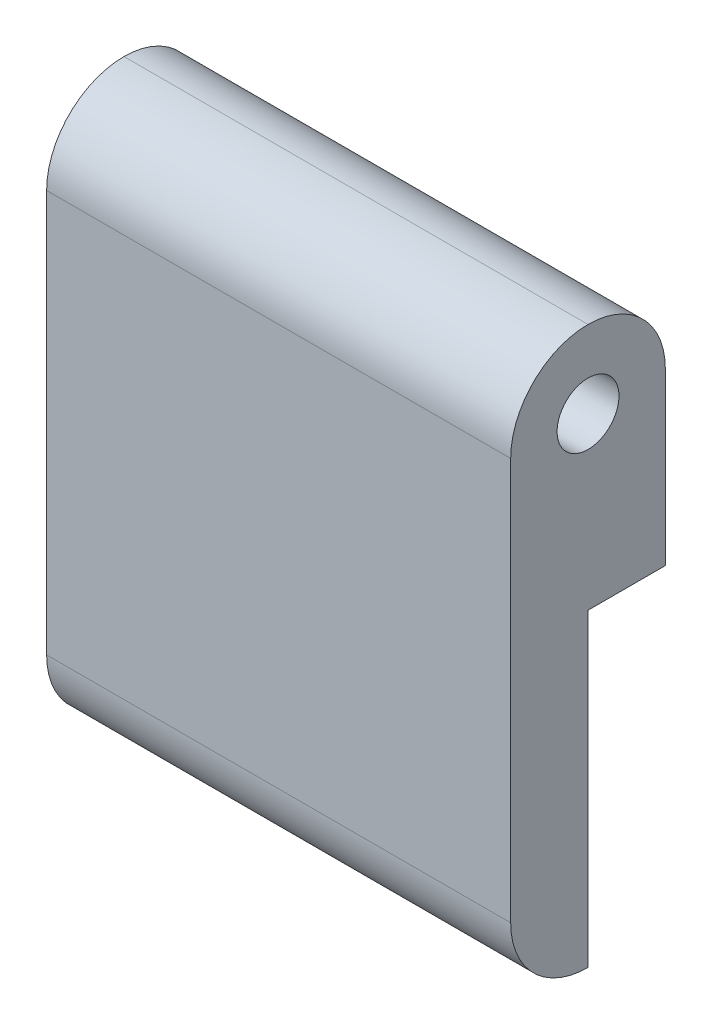
SolidWorks part; units mm, degrees
ref_plane "Front Plane" through (0, 0, 0) normal (0, 0, 1) x (1, 0, 0)
ref_plane "Top Plane" through (0, 0, 0) normal (0, 1, 0) x (1, 0, 0)
ref_plane "Right Plane" through (0, 0, 0) normal (1, 0, 0) x (0, 0, -1)
sketch "Sketch1" plane through (0, 0, 0) normal (0, 0, 1) x (1, 0, 0)
  line L1 (-7.5, -4) -> (7.5, -4)
  line L2 (-7.5, -4) -> (-7.5, 4)
  line L3 (-7.5, 4) -> (7.5, 4)
  line L4 (7.5, -4) -> (7.5, 4)
  line L5 (-7.5, -4) -> (7.5, 4) construction
  line L6 (-7.5, 4) -> (7.5, -4) construction
  point P0 (0, 0)
  dimension "D1" = 15
  dimension "D2" = 8
extrude "Boss-Extrude1" add sketch "Sketch1" along normal blind 5
sketch "Sketch2" plane through (0, -4, 0) normal (0, -1, 0) x (1, 0, 0)
  line L0 (7.5, 5) -> (7.5, 0) construction
  line L2 (7.5, 2.5) -> (-7.5, 2.5)
  line L3 (7.5, 2.5) -> (7.5, 5)
  line L4 (7.5, 5) -> (-7.5, 5)
  line L5 (-7.5, 2.5) -> (-7.5, 5)
extrude "Boss-Extrude2" add sketch "Sketch2" along normal blind 10
sketch "Sketch4" plane through (7.5, 0, 0) normal (1, 0, 0) x (0, 0, -1)
  line L0 (-5, 4) -> (0, 4) construction
  circle A0 centre (-2.5, 1.5) radius 1
  dimension "D1" = 2.5
extrude "Cut-Extrude1" cut sketch "Sketch4" against normal through all
fillet "Fillet1" radius 2.5 3 edges at (0, -14, 5) (0, 4, 0) (0, 4, 5)
